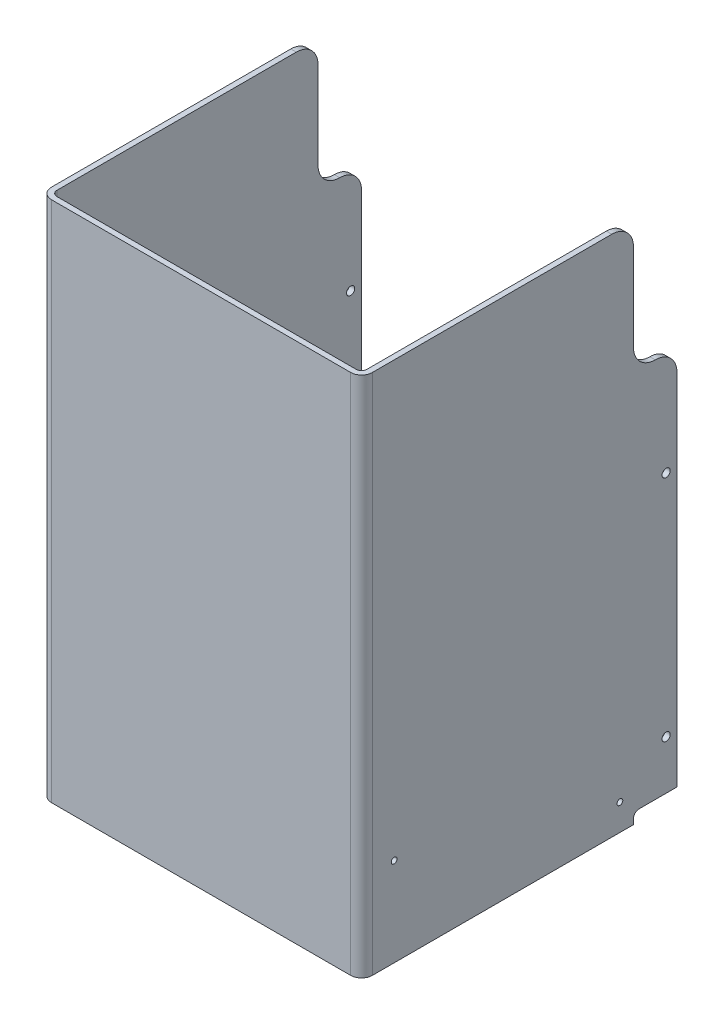
SolidWorks part; units mm, degrees
material "PC High Viscosity"
ref_plane "Front Plane" through (0, 0, 0) normal (0, 0, 1) x (1, 0, 0)
ref_plane "Top Plane" through (0, 0, 0) normal (0, 1, 0) x (1, 0, 0)
ref_plane "Right Plane" through (0, 0, 0) normal (1, 0, 0) x (0, 0, -1)
sketch "Sketch1" plane through (0, 0, 0) normal (0, 1, 0) x (1, 0, 0)
  line L0 (0, 0) -> (0, -368.3)
  line L1 (0, -368.3) -> (374.65, -368.3)
  line L2 (374.65, -368.3) -> (374.65, 0)
  line L3 (374.65, 0) -> (368.3, 0)
  line L4 (368.3, 0) -> (368.3, -361.95)
  line L5 (368.3, -361.95) -> (6.35, -361.95)
  line L6 (6.35, -361.95) -> (6.35, 0)
  line L7 (6.35, 0) -> (0, 0)
  dimension "D1" = 361.95
  dimension "D2" = 361.95
  dimension "D3" = 6.35
  dimension "D4" = 6.35
extrude "Boss-Extrude1" add sketch "Sketch1" along normal blind 609.6
fillet "Fillet1" radius 6.35 2 edges at (368.3, 304.8, 361.95) (6.35, 304.8, 361.95)
fillet "Fillet2" radius 12.7 2 edges at (374.65, 304.8, 368.3) (0, 304.8, 368.3)
sketch "Sketch2" plane through (374.65, 0, 0) normal (1, 0, 0) x (0, 0, -1)
  line L0 (0, 0) -> (-50.8, 0)
  line L1 (0, 0) -> (0, 12.7)
  line L2 (-50.8, 0) -> (-50.8, 12.7)
  line L3 (0, 12.7) -> (-50.8, 12.7)
  line L4 (-355.6, 0) -> (0, 0) construction
  dimension "D1" = 12.7
  dimension "D2" = 50.8
extrude "Cut-Extrude1" cut sketch "Sketch2" against normal through all
sketch "Sketch4" plane through (374.65, 0, 0) normal (1, 0, 0) x (0, 0, -1)
  line L1 (0, 609.6) -> (-50.8, 609.6)
  line L2 (0, 609.6) -> (0, 457.2)
  line L3 (0, 457.2) -> (-50.8, 457.2)
  line L4 (-50.8, 609.6) -> (-50.8, 457.2)
  dimension "D1" = 50.8
  dimension "D2" = 152.4
extrude "Cut-Extrude2" cut sketch "Sketch4" against normal through all
sketch "Sketch5" plane through (374.65, 0, 0) normal (1, 0, 0) x (0, 0, -1)
  line L0 (-0.8443, 19.1643) -> (0, 22.225) construction
  line L1 (-0.8443, 19.1643) -> (-346.7012, 114.5712) construction
  line L2 (0, 22.225) -> (-345.8569, 117.6319) construction
  line L3 (-346.7012, 114.5712) -> (-345.8569, 117.6319) construction
  line L5 (-355.6, 0) -> (-50.8, 0) construction
  line L6 (-330.2, 103.4321) -> (-66.675, 30.737) construction
  line L7 (0, 457.2) -> (0, 12.7) construction
  line L8 (0, 12.7) -> (-50.8, 12.7) construction
  circle A0 centre (-330.2, 103.4321) radius 3.3782
  circle A1 centre (-66.675, 30.737) radius 3.3782
  point P14 (0, 0)
  point P15 (0, 0)
  dimension "D4" = 6.35
  dimension "D5" = 6.7564
  dimension "D1" = 3.175
  dimension "D2" = 9.525
  dimension "D3" = 358.775
  dimension "D6" = 66.675
  dimension "D7" = 330.2
  dimension "D8" = 103.4321
extrude "Cut-Extrude3" cut sketch "Sketch5" against normal through all
sketch "Sketch6" plane through (374.65, 0, 0) normal (1, 0, 0) x (0, 0, -1)
  line L0 (0, 12.7) -> (-50.8, 12.7) construction
  line L2 (0, 457.2) -> (0, 12.7) construction
  circle A0 centre (-12.7, 69.85) radius 4.7625
  circle A1 centre (-12.7, 336.55) radius 4.7625
  dimension "D1" = 57.15
  dimension "D3" = 9.525
  dimension "D2" = 266.7
  dimension "D4" = 12.7
extrude "Cut-Extrude4" cut sketch "Sketch6" against normal through all
fillet "Fillet3" radius 25.4 6 edges at (3.175, 457.2, 0) (371.475, 457.2, 0) (371.475, 457.2, 50.8) (3.175, 457.2, 50.8) (3.175, 609.6, 50.8) (371.475, 609.6, 50.8)
fillet "Fillet4" radius 6.35 2 edges at (3.175, 12.7, 50.8) (371.475, 12.7, 50.8)
